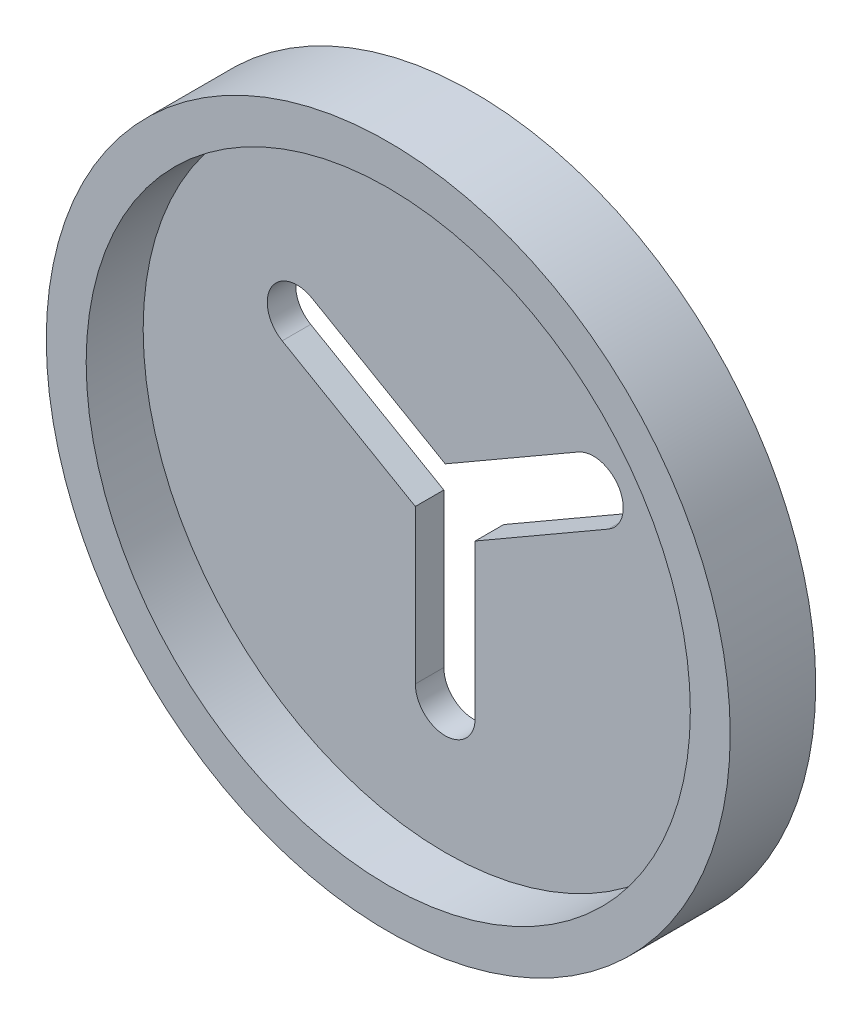
SolidWorks part; units mm, degrees
ref_plane "Alzado" through (0, 0, 0) normal (0, 0, 1) x (1, 0, 0)
ref_plane "Planta" through (0, 0, 0) normal (0, 1, 0) x (1, 0, 0)
ref_plane "Vista lateral" through (0, 0, 0) normal (1, 0, 0) x (0, 0, -1)
sketch "Croquis1" plane through (0, 0, 0) normal (0, 0, 1) x (1, 0, 0)
  circle A0 centre (0, 0) radius 55
  dimension "D1" = 110
extrude "Disco" add sketch "Croquis1" along normal blind 5
sketch "Croquis6" plane through (0, 0, 5) normal (0, 0, 1) x (1, 0, 0)
  line L0 (-5.25, 0) -> (-5.25, -30)
  line L1 (5.25, 0) -> (5.25, -30)
  line L2 (2.625, 4.5466) -> (-23.3558, 19.5466)
  line L3 (-2.625, -4.5466) -> (-28.6058, 10.4534)
  line L4 (2.625, -4.5466) -> (28.6058, 10.4534)
  line L5 (-2.625, 4.5466) -> (23.3558, 19.5466)
  arc A1 (-5.25, 0) -> (5.25, 0) centre (0, 0) cw
  arc A2 (-5.25, -30) -> (5.25, -30) centre (0, -30) ccw
  arc A3 (2.625, 4.5466) -> (-2.625, -4.5466) centre (0, 0) cw
  arc A4 (-23.3558, 19.5466) -> (-28.6058, 10.4534) centre (-25.9808, 15) ccw
  arc A5 (2.625, -4.5466) -> (-2.625, 4.5466) centre (0, 0) cw
  arc A6 (28.6058, 10.4534) -> (23.3558, 19.5466) centre (25.9808, 15) ccw
  point P22 (0, 0)
  dimension "D1" = 30
  dimension "D3" = 5.25
  dimension "D2" = 3
extrude "Cortar-Extruir1" cut sketch "Croquis6" against normal blind 10 contours L2 A4 L3 A3 | L5 A6 L4 A5 | L1 A2 L0 A1
sketch "Croquis7" plane through (0, 0, 5) normal (0, 0, 1) x (1, 0, 0)
  circle A0 centre (0, 0) radius 53
  circle A1 centre (0, 0) radius 60
  circle A2 centre (0, 0) radius 53
  circle M3 centre (0, 0) radius 55
  dimension "D1" = 120
  dimension "D2" = 106
extrude "Saliente-Extruir1" add sketch "Croquis7" along normal blind 10 and the other way through all contours A0 M3 | A1 M3 region at (-58.3029, 0, 5) region at (-53.4444, 0, 5)
